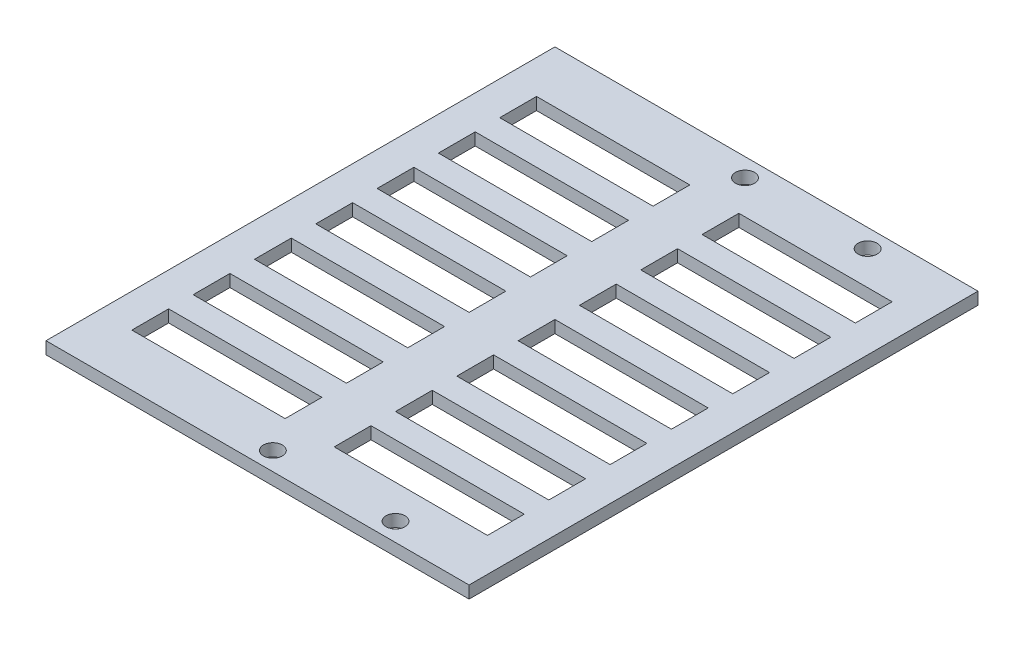
SolidWorks part; units mm, degrees
material "PE 低密度结膜"
ref_plane "前视基准面" through (0, 0, 0) normal (0, 0, 1) x (1, 0, 0)
ref_plane "上视基准面" through (0, 0, 0) normal (0, 1, 0) x (1, 0, 0)
ref_plane "右视基准面" through (0, 0, 0) normal (1, 0, 0) x (0, 0, -1)
sketch "草图2" plane through (0, 0, 0) normal (0, 1, 0) x (1, 0, 0)
  line L1 (0, 0) -> (-69, 0)
  line L2 (0, 0) -> (0, 83)
  line L3 (0, 83) -> (-69, 83)
  line L4 (-69, 0) -> (-69, 83)
  dimension "D1" = 69
  dimension "D2" = 83
extrude "凸台-拉伸1" add sketch "草图2" along normal blind 2
sketch "草图3" plane through (0, 2, 0) normal (0, 1, 0) x (1, 0, 0)
  circle A0 centre (-35, 80) radius 1.55
  circle A1 centre (-15, 80) radius 1.55
  circle A2 centre (-15, 3) radius 1.55
  circle A3 centre (-35, 3) radius 1.55
extrude "切除-拉伸1" cut sketch "草图3" against normal blind 14
sketch "Sketch1" plane through (0, 2, 0) normal (0, 1, 0) x (1, 0, 0)
  line L0 (-69, 41.5) -> (0, 41.5) construction
  line L1 (-69, 83) -> (-69, 0) construction
  line L2 (0, 0) -> (0, 83) construction
  line L4 (-30.5, 44.5) -> (-5.5, 44.5)
  line L5 (-30.5, 44.5) -> (-30.5, 38.5)
  line L6 (-30.5, 38.5) -> (-5.5, 38.5)
  line L7 (-5.5, 44.5) -> (-5.5, 38.5)
  line L8 (-30.5, 44.5) -> (-5.5, 38.5) construction
  line L9 (-30.5, 38.5) -> (-5.5, 44.5) construction
  line L10 (-63.5, 44.5) -> (-38.5, 44.5)
  line L11 (-63.5, 44.5) -> (-63.5, 38.5)
  line L12 (-63.5, 38.5) -> (-38.5, 38.5)
  line L13 (-38.5, 44.5) -> (-38.5, 38.5)
  line L14 (-63.5, 44.5) -> (-38.5, 38.5) construction
  line L15 (-63.5, 38.5) -> (-38.5, 44.5) construction
  point P6 (-18, 41.5)
  point P11 (-51, 41.5)
  dimension "D1" = 18
  dimension "D2" = 18
  dimension "D3" = 6
  dimension "D4" = 6
  dimension "D5" = 25
  dimension "D6" = 25
extrude "Cut-Extrude1" cut sketch "Sketch1" against normal blind 10
pattern_linear "LPattern1" count 4 spacing 10 along (0, 0, 1) of "Cut-Extrude1"
pattern_linear "LPattern2" count 4 spacing 10 along (0, 0, -1) of "LPattern1"
